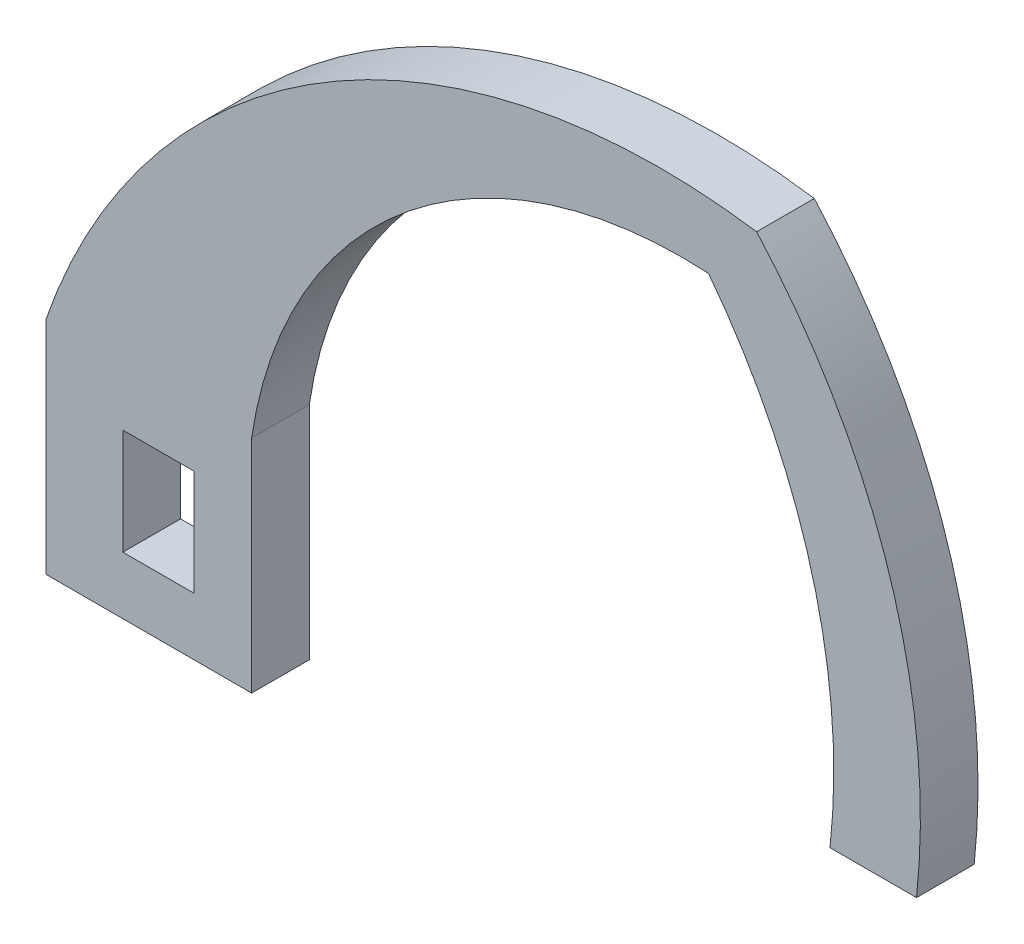
SolidWorks part; units mm, degrees
ref_plane "Front Plane" through (0, 0, 0) normal (0, 0, 1) x (1, 0, 0)
ref_plane "Top Plane" through (0, 0, 0) normal (0, 1, 0) x (1, 0, 0)
ref_plane "Right Plane" through (0, 0, 0) normal (1, 0, 0) x (0, 0, -1)
sketch "Sketch1" plane through (0, 0, 0) normal (0, 0, 1) x (1, 0, 0)
  line L1 (-1.85, 2.75) -> (1.85, 2.75)
  line L2 (-1.85, 2.75) -> (-1.85, -2.75)
  line L3 (-1.85, -2.75) -> (1.85, -2.75)
  line L4 (1.85, 2.75) -> (1.85, -2.75)
  line L6 (4.85, 5.75) -> (4.85, -5.75)
  line L7 (4.85, -5.75) -> (-5.85, -5.75)
  line L8 (-5.85, -5.75) -> (-5.85, 5.75)
  line L18 (34.939, 2.3297) -> (39.4408, 2.3297)
  arc A7 (31.1232, 28.1736) -> (-5.85, 5.75) centre (26.1434, -5.309) ccw
  arc A8 (4.85, 5.75) -> (28.6199, 25.0444) centre (27.2524, 2.4402) cw
  arc A10 (39.4408, 2.3297) -> (31.1232, 28.1736) centre (6.4632, 5.9766) ccw
  arc A11 (34.939, 2.3297) -> (28.6199, 25.0444) centre (3.5958, 5.8465) ccw
  point P4 (0, 2.75)
  point P6 (-1.85, 0)
  point P7 (31.1232, 27.7602)
  dimension "D1" = 5.5
  dimension "D2" = 3.7
  dimension "D4" = 3
  dimension "D5" = 3
extrude "Boss-Extrude1" add sketch "Sketch1" along normal blind 3
sketch "Sketch2" plane through (0, 0, 3) normal (0, 0, 1) x (1, 0, 0)
  line L0 (0, 2.75) -> (0, -2.75) construction
  line L1 (1.85, 2.75) -> (-1.85, 2.75) construction
  line L2 (-1.85, -2.75) -> (1.85, -2.75) construction
  line L3 (-1.85, 0) -> (1.85, 0) construction
  line L4 (-1.85, 2.75) -> (-1.85, -2.75) construction
  line L5 (1.85, -2.75) -> (1.85, 2.75) construction
  point P12 (0, 2.75)
